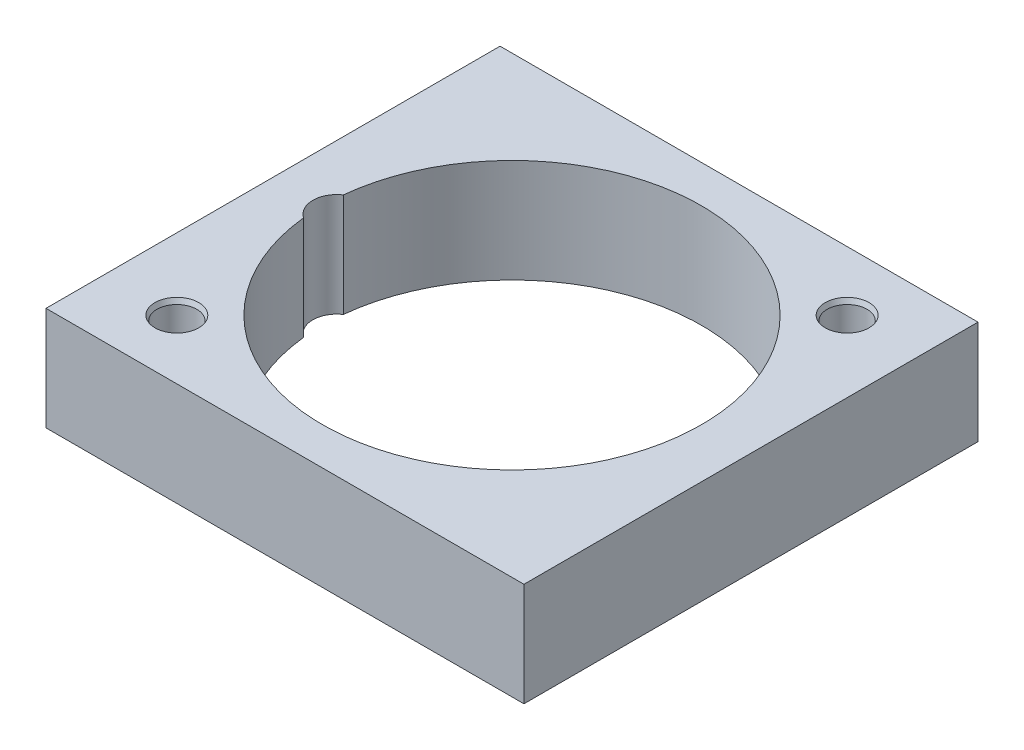
SolidWorks part; units mm, degrees
ref_plane "Face" through (0, 0, 0) normal (0, 0, 1) x (1, 0, 0)
ref_plane "Dessus" through (0, 0, 0) normal (0, 1, 0) x (1, 0, 0)
ref_plane "Droite" through (0, 0, 0) normal (1, 0, 0) x (0, 0, -1)
sketch "Esquisse1" plane through (0, 0, 0) normal (0, 1, 0) x (1, 0, 0)
  line L0 (44.222, 0) -> (-47.4621, 0) construction
  line L1 (30, -28.5) -> (-30, -28.5)
  line L2 (-30, -28.5) -> (-30, 28.5)
  line L3 (30, -28.5) -> (30, 28.5)
  line L4 (30, 28.5) -> (-30, 28.5)
  arc A0 (-23.6691, 2.4928) -> (-23.6691, -2.4928) centre (0, 0) cw
  arc A1 (-23.6691, -2.4928) -> (-23.6691, 2.4928) centre (-22, 0) cw
  point P14 (-30, 0)
  point P15 (30, 0)
  dimension "D1" = 30
  dimension "D2" = 30
  dimension "D3" = 28.5
  dimension "D4" = 23.8
  dimension "D6" = 3
  dimension "D5" = 22
extrude "Base-Extrusion" add sketch "Esquisse1" along normal blind 13
ref_axis "Axe1" through (-80, 13, 0) along (1, 0, 0)
sketch "Esquisse2" plane through (0, 13, 0) normal (0, 1, 0) x (-1, 0, 0)
  line L1 (0, 0) -> (-21.0364, -21.0364) construction
  line L2 (80, 0) -> (-170, 0) construction
  dimension "D2" = 29.75
  dimension "D3" = 45
hole_wizard "Dégagement pour M51" positions "Esquisse7" profile "Esquisse6" hole size "M5" standard "ISO"
sketch "Esquisse7" plane through (0, 13, 0) normal (0, 1, 0) x (-1, 0, 0)
  point P0 (-21.0364, -21.0364)
sketch "Esquisse6" plane through (21.0364, 13, -21.0364) normal (1, 0, 0) x (0, 0, 1)
  line L0 (0, 0) -> (0, 9.5022)
  line L1 (0, 9.5022) -> (2.5, 8)
  line L2 (2.5, 8) -> (2.5, 0.6036)
  line L3 (2.5, 0.6036) -> (2.75, 0)
  line L5 (2.75, 0) -> (0, 0)
  line L6 (-2.5, 0.6036) -> (-2.75, 0) construction
  line L10 (0, 9.5022) -> (-2.5, 8) construction
  line L11 (0, -6.35) -> (0, 107.95) construction
  dimension "Diamètre du perçage" = 5
  dimension "Profondeur du perçage" = 8
  dimension "Diamètre du fraisage entrant" = 5.5
  dimension "Angle du fraisage entrant" = 45
  dimension "Angle de pointe" = 118
ref_axis "Axe2" through (0, 63, 0) along (0, -1, 0)
pattern_circular "Répétition circulaire1" count 2 every 180 about axis through (0, 63, 0) along (0, -1, 0) of "Dégagement pour M51"
sketch "Esquisse8" plane through (0, 0, 28.5) normal (0, 0, 1) x (1, 0, 0)
  point P2 (0, 0)
